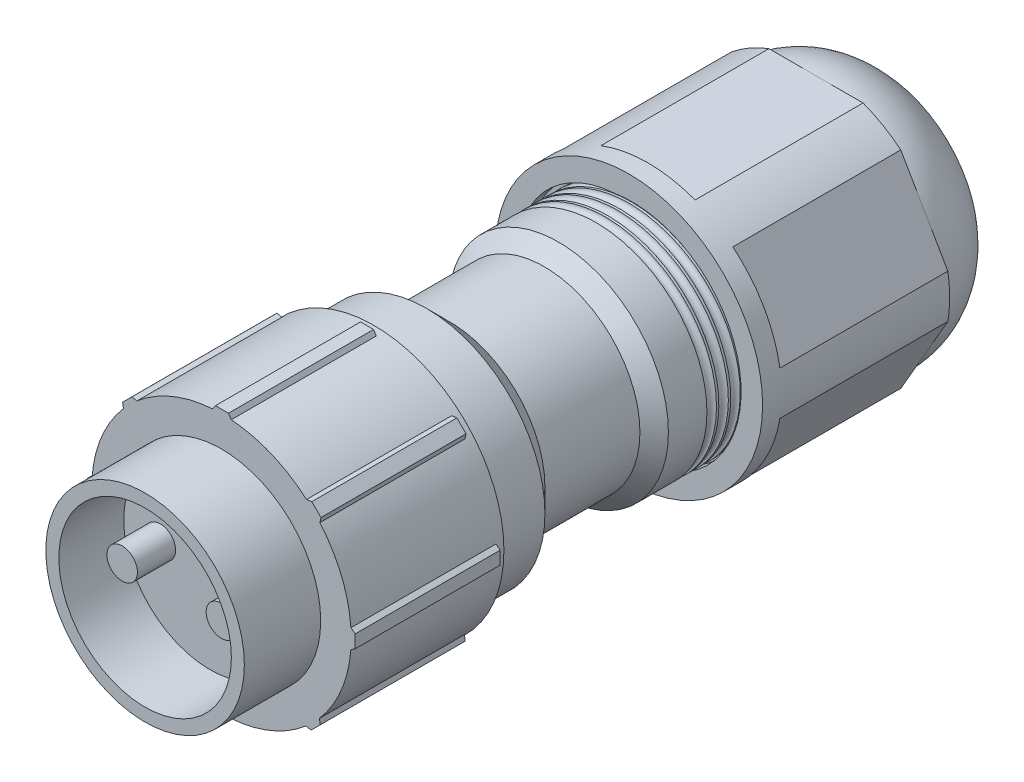
SolidWorks part; units mm, degrees
ref_plane "Front Plane" through (0, 0, 0) normal (0, 0, 1) x (1, 0, 0)
ref_plane "Top Plane" through (0, 0, 0) normal (0, 1, 0) x (1, 0, 0)
ref_plane "Right Plane" through (0, 0, 0) normal (1, 0, 0) x (0, 0, -1)
sketch "Sketch1" plane through (0, 0, 0) normal (0, 0, 1) x (1, 0, 0)
  circle A0 centre (0, 0) radius 8.5
  dimension "D1" = 17
extrude "Boss-Extrude1" add sketch "Sketch1" against normal blind 10
sketch "Sketch2" plane through (0, 0, 0) normal (0, 0, 1) x (1, 0, 0)
  circle A0 centre (0, 0) radius 6.5
  dimension "D1" = 13
extrude "Boss-Extrude2" add sketch "Sketch2" along normal blind 5
sketch "Sketch3" plane through (0, 0, 0) normal (1, 0, 0) x (0, 0, -1)
  line L0 (10, 7.7662) -> (13.4193, 7.7662)
  line L2 (10, -8.5) -> (10, 8.5) construction
  line L3 (13.4193, 7.7662) -> (14.9223, 6.2632)
  line L4 (14.9223, 6.2632) -> (21.1445, 6.2632)
  line L5 (21.1445, 6.2632) -> (22.0763, 7.195)
  line L6 (22.0763, 7.195) -> (23.94, 7.195)
  line L7 (23.94, 7.195) -> (23.94, 0)
  line L8 (23.94, 0) -> (10, 0)
  line L9 (10, 0) -> (10, 7.7662)
revolve "Revolve1" add sketch "Sketch3" angle 360 about L8
sketch "Sketch4" plane through (0, 0, -23.94) normal (0, 0, -1) x (-1, 0, 0)
  circle A0 centre (0, 0) radius 7.195
extrude "Boss-Extrude3" add sketch "Sketch4" along normal blind 3.5
sketch "Sketch5" plane through (0, 0, -27.44) normal (0, 0, -1) x (-1, 0, 0)
  circle A0 centre (0, 0) radius 7.195 construction
  circle A1 centre (0, 0) radius 7.195
curve "Helix/Spiral1" pitch 0.7778 height 3.5 turns 4.5
sketch "Sketch6" plane through (0, 0, 0) normal (1, 0, 0) x (0, 0, -1)
  circle A1 centre (27.44, -7.195) radius 0.3122
sweep "Cut-Sweep2" cut profiles "Sketch6" path "Helix/Spiral1"
sketch "Sketch7" plane through (0, 0, -27.44) normal (0, 0, -1) x (-1, 0, 0)
  circle A0 centre (0, 0) radius 8.75
  dimension "D1" = 17.5
extrude "Boss-Extrude5" add sketch "Sketch7" along normal blind 11.5
sketch "Sketch8" plane through (0, 0, 0) normal (1, 0, 0) x (0, 0, -1)
  line L0 (38.94, -8.75) -> (38.94, 8.75) construction
  line L2 (38.94, 0) -> (38.94, 8.1909)
  line L4 (41.9978, 0) -> (38.94, 0)
  line L5 (43.1551, 6.3625) -> (43.1551, 0)
  line L6 (43.1551, 0) -> (41.9978, 0)
  arc A0 (38.94, 8.1909) -> (43.1551, 6.3625) centre (39.249, 3.1304) cw
revolve "Revolve3" add sketch "Sketch8" angle 360 about L4
sketch "Sketch10" plane through (0, 0, -43.1551) normal (0, 0, -1) x (-1, 0, 0)
  circle A0 centre (0, 0) radius 3
  dimension "D1" = 6
extrude "Cut-Extrude1" cut sketch "Sketch10" against normal blind 3
sketch "Sketch11" plane through (0, 0, 5) normal (0, 0, 1) x (1, 0, 0)
  circle A0 centre (0, 0) radius 5.65
  dimension "D1" = 11.3
extrude "Cut-Extrude2" cut sketch "Sketch11" against normal blind 4.25
sketch "Sketch12" plane through (0, 0, 0.75) normal (0, 0, 1) x (1, 0, 0)
  circle A1 centre (-3.25, 0) radius 1
  dimension "D1" = 3.25
  dimension "D2" = 2
extrude "Boss-Extrude6" add sketch "Sketch12" along normal blind 2.5
sketch "Sketch14" plane through (0, 0, 0) normal (0, 0, 1) x (1, 0, 0)
  line L10 (0.0229, 8.5) -> (0.0229, 8.4712)
  line L11 (0.0229, 8.4712) -> (0.6429, 8.4757)
  line L12 (0.0229, 8.4712) -> (-0.5971, 8.479)
  line L13 (-0.5971, 8.479) -> (-0.3883, 8.759)
  line L14 (0.6429, 8.4757) -> (0.4618, 8.7557)
  line L15 (-0.3883, 8.759) -> (0.4618, 8.7557)
  circle A3 centre (0, 0) radius 8.5 construction
  dimension "D1" = 0.62
  dimension "D2" = 0.62
  dimension "D3" = 0.28
  dimension "D4" = 0.28
extrude "Boss-Extrude7" add sketch "Sketch14" against normal blind 9.5
pattern_circular "CirPattern2" count 8 over 360 about axis through (0, 0, 0) along (0, 0, 1) of "Boss-Extrude7"
sketch "Sketch15" plane through (0, 0, -27.44) normal (0, 0, 1) x (1, 0, 0)
  arc A0 (-0.9885, 8.694) -> (-8.75, 0) centre (0, 0) ccw
  circle A1 centre (0, 0) radius 8.75 construction
  arc A2 (-8.75, 0) -> (-0.3082, -8.7446) centre (0, 0) ccw
  arc A3 (8.75, 0) -> (-0.3082, -8.7446) centre (0, 0) cw
  arc A4 (8.75, 0) -> (-0.9885, 8.694) centre (0, 0) ccw
  arc A5 (-0.9885, 7.1742) -> (-7.2763, 0) centre (-0.5453, 0.4432) ccw
  arc A6 (-7.2763, 0) -> (-2.2166, -7.0118) centre (-0.132, -0.1761) ccw
  arc A7 (-2.2166, -7.0118) -> (7.0803, 2.028) centre (-0.0575, 0.0683) ccw
  arc A8 (7.0803, 2.028) -> (-0.9885, 7.1742) centre (0.2001, 0.139) ccw
extrude "Boss-Extrude8" add sketch "Sketch15" along normal blind 0.75
sketch "Sketch16" plane through (0, 0, -38.94) normal (0, 0, -1) x (-1, 0, 0)
  line L0 (-0.0296, 8.8518) -> (-3.5296, 8.8518)
  line L1 (-3.5296, 8.8518) -> (-3.5296, 8.1896)
  line L2 (-0.0296, 8.8518) -> (3.4704, 8.8518)
  line L3 (-3.5296, 8.1896) -> (3.4704, 8.1896)
  line L4 (3.4704, 8.1896) -> (3.4704, 8.8518)
  dimension "D1" = 3.5
  dimension "D2" = 3.5
  dimension "D3" = 7
extrude "Cut-Extrude3" cut sketch "Sketch16" against normal blind 11
pattern_circular "CirPattern3" count 6 over 360 about axis through (0, 0, 0) along (0, 0, 1) of "Cut-Extrude3"
sketch "Sketch17" plane through (0, 0, 0.75) normal (0, 0, 1) x (1, 0, 0)
  circle A0 centre (3.25, 0) radius 1
  dimension "D1" = 2
  dimension "D2" = 3.25
extrude "Boss-Extrude9" add sketch "Sketch17" along normal blind 2.5
